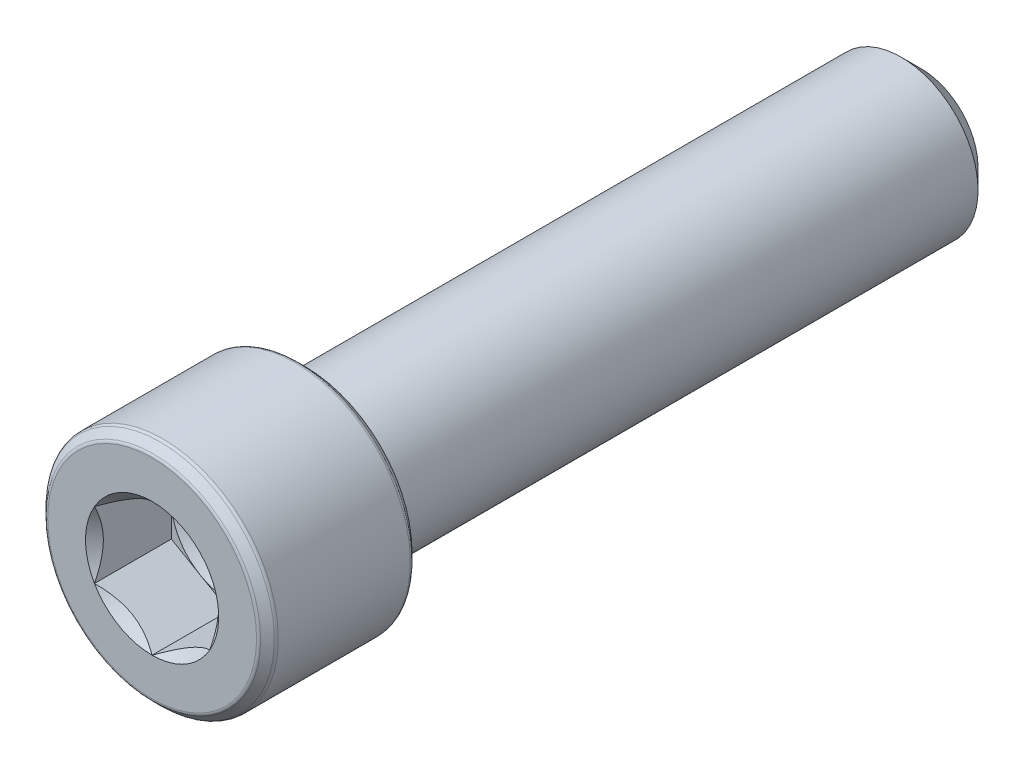
SolidWorks part; units mm, degrees
ref_plane "Front Plane" through (0, 0, 0) normal (0, 0, 1) x (1, 0, 0)
ref_plane "Top Plane" through (0, 0, 0) normal (0, 1, 0) x (1, 0, 0)
ref_plane "Right Plane" through (0, 0, 0) normal (1, 0, 0) x (0, 0, -1)
sketch "Sketch1" plane through (0, 0, 0) normal (1, 0, 0) x (0, 0, -1)
  line L0 (-15.875, 0) -> (15.875, 0) construction
  line L1 (-15.875, -4.7625) -> (-15.875, 4.7625) construction
  line L2 (-15.875, 4.7625) -> (-9.525, 4.7625) construction
  line L3 (-9.525, 4.7625) -> (-9.525, 3.175) construction
  line L4 (-9.525, 3.175) -> (15.0501, 3.175) construction
  line L5 (15.7956, 3.3125) -> (16.4306, 2.2126) construction
  line L6 (16.4306, 2.2126) -> (17.0656, 3.3125) construction
  line L7 (17.0656, 3.3125) -> (15.7956, 3.3125) construction
  line L8 (15.0501, 3.175) -> (15.875, 2.3501) construction
  line L9 (15.875, 2.3501) -> (15.875, 0) construction
  line L10 (15.875, 3.175) -> (16.9863, 3.175) construction
  line L11 (16.4306, 3.3125) -> (16.4306, 3.175) construction
  line L12 (16.4306, 3.175) -> (16.4306, 2.3501) construction
  line L13 (16.4306, 2.3501) -> (16.4306, 2.2126) construction
  line L14 (16.3513, 2.3501) -> (16.51, 2.3501) construction
  line L15 (15.8353, 3.2437) -> (17.0259, 3.2437) construction
  line L16 (16.51, 2.3501) -> (17.0259, 3.2437) construction
  line L17 (16.3513, 2.3501) -> (15.8353, 3.2437) construction
  line L18 (-15.875, 2.3812) -> (-12.7, 2.3812) construction
  line L19 (-12.7, 2.3812) -> (-12.7, 0) construction
  line L20 (12.7, 3.175) -> (12.7, -3.175) construction
  line L21 (-15.875, -2.3813) -> (-15.875, 2.3812) construction
  line L22 (15.875, -3.175) -> (15.875, 3.175) construction
  point P20 (16.4306, 3.2437)
  point P22 (12.7, -3.175)
  point P28 (12.7, 0)
  point P29 (15.0501, -3.175)
  point P30 (-11.1125, 4.7625)
  point P36 (-15.875, 0)
  point P38 (15.875, 0)
  dimension "Length" = 25.4
  dimension "Head Height" = 6.35
  dimension "D1" = 45
  dimension "Thread Pitch" = 1.27
  dimension "D3" = 0.1588
  dimension "D4" = 3.175
  dimension "D5" = 3.175
  dimension "D2" = 4.7625
  dimension "Head Diameter" = 9.525
  dimension "Drive Size" = 4.7625
  dimension "Screw Size Decimal Equivalent" = 6.35
sketch "Sketch3" plane through (0, 0, 0) normal (1, 0, 0) x (0, 0, -1)
  line L0 (-15.875, 4.3125) -> (-15.875, 2.3812)
  line L1 (-15.875, 2.3812) -> (-12.7, 2.3812)
  line L2 (-12.7, 2.3812) -> (-12.7, 0)
  line L3 (-12.7, 0) -> (15.875, 0)
  line L4 (15.875, 0) -> (15.875, 2.3501)
  line L5 (15.875, 2.3501) -> (15.0501, 3.175)
  line L6 (15.0501, 3.175) -> (-9.525, 3.175)
  line L7 (-9.525, 3.175) -> (-9.525, 4.3125)
  line L8 (-9.975, 4.7625) -> (-15.425, 4.7625)
  line L9 (-15.8262, 4.4303) -> (-15.5428, 4.7137)
  line L10 (-9.8572, 4.7137) -> (-9.5738, 4.4303)
  line L11 (-15.875, 4.7625) -> (-9.525, 4.7625) construction
  arc A0 (-15.5428, 4.7137) -> (-15.425, 4.7625) centre (-15.425, 4.5958) cw
  arc A1 (-15.8262, 4.4303) -> (-15.875, 4.3125) centre (-15.7083, 4.3125) ccw
  arc A2 (-9.5738, 4.4303) -> (-9.525, 4.3125) centre (-9.6917, 4.3125) cw
  arc A3 (-9.8572, 4.7137) -> (-9.975, 4.7625) centre (-9.975, 4.5958) ccw
  point P25 (-15.875, 4.3815)
  dimension "D1" = 45
  dimension "D3" = 0.1667
  dimension "D2" = 0.381
revolve "Revolve1" add sketch "Sketch3" angle 360 about L0
sketch "Sketch4" plane through (0, 0, 15.875) normal (0, 0, 1) x (1, 0, 0)
  line L1 (0, 2.7496) -> (-2.3812, 1.3748)
  line L2 (-2.3812, 1.3748) -> (-2.3812, -1.3748)
  line L3 (-2.3812, -1.3748) -> (0, -2.7496)
  line L4 (0, -2.7496) -> (2.3812, -1.3748)
  line L5 (2.3812, -1.3748) -> (2.3812, 1.3748)
  line L6 (2.3812, 1.3748) -> (0, 2.7496)
  circle A0 centre (0, 0) radius 2.3812 construction
extrude "Cut-Extrude1" cut sketch "Sketch4" against normal up to vertex (3.175 mm away) up to point (0, 2.3812, 12.7)
sketch "Sketch5" plane through (0, 0, 15.875) normal (0, 0, 1) x (1, 0, 0)
  circle A0 centre (0, 0) radius 2.7496
extrude "Cut-Extrude2" cut sketch "Sketch5" against normal up to next (3.175 mm away) draft 45
sketch "Sketch10" plane through (0, 0, 12.7) normal (0, 0, 1) x (1, 0, 0)
  line L0 (2.3812, 1.3748) -> (2.3812, -1.3748) construction
  circle A0 centre (0, 0) radius 2.3812
extrude "Cut-Extrude3" cut sketch "Sketch10" against normal through all draft 60
ref_plane "Plane1" [suppressed] through (0, 0, 9.3663) normal (0, 0, -1) x (-1, 0, 0)
split "Split1" [suppressed] bodies to split 112
sketch "Sketch6" [suppressed] plane through (0, 0, -15.875) normal (0, 0, -1) x (-1, 0, 0)
  circle A0 centre (0, 0) radius 3.175 construction
  circle A1 centre (0, 0) radius 3.175
curve "Helix/Spiral1" [suppressed] pitch 1.27 height 26.67 turns 21
sketch "Sketch7" [suppressed] plane through (0, 0, 0) normal (1, 0, 0) x (0, 0, -1)
  line L0 (16.3513, 2.3501) -> (16.51, 2.3501) construction
  line L1 (16.3513, 2.3501) -> (15.8353, 3.2437) construction
  line L2 (15.8353, 3.2437) -> (17.0259, 3.2437) construction
  line L3 (16.51, 2.3501) -> (17.0259, 3.2437) construction
  line L4 (16.3513, 2.3501) -> (16.51, 2.3501)
  line L5 (16.3513, 2.3501) -> (15.8353, 3.2437)
  line L6 (15.8353, 3.2437) -> (17.0259, 3.2437)
  line L7 (16.51, 2.3501) -> (17.0259, 3.2437)
sweep "Cut-Sweep1" [suppressed] cut profiles "Sketch7" path "Helix/Spiral1"
sketch "Sketch14" [suppressed] plane through (0, 0, 9.3663) normal (0, 0, -1) x (-1, 0, 0)
  circle A1 centre (0, 0) radius 3.175
  circle A2 centre (0, 0) radius 3.175
  dimension "D1" = 0
extrude "Boss-Extrude2" [suppressed] add sketch "Sketch14" along normal through all draft 60.148
sketch "Sketch12" [suppressed] plane through (0, 0, 15.875) normal (0, 0, 1) x (1, 0, 0)
  line L0 (0, 0) -> (0, 4.7625) construction
  line L1 (0, 0) -> (0.2381, 5.0858) construction
  line L2 (0.2381, 5.0858) -> (-0.2381, 5.0858)
  line L3 (-0.2381, 5.0858) -> (0, 0) construction
  line L4 (-0.2381, 5.0858) -> (-0.055, 4.6461)
  line L5 (0.055, 4.6461) -> (0.2381, 5.0858)
  line L7 (0, 4.3125) -> (0, 4.4303) construction
  circle A0 centre (0, 0) radius 4.7625 construction
  arc A2 (-0.055, 4.6461) -> (0.055, 4.6461) centre (0, 4.669) ccw
  point P11 (0, 4.5143)
  point P13 (0, 4.6095)
  point P17 (0, 4.3714)
  dimension "D3" = 0.0595
  dimension "D1" = 0.4763
  dimension "D2" = 5.361
  dimension "D5" = 0.2381
extrude "Cut-Extrude4" [suppressed] cut sketch "Sketch12" against normal blind 4.7625
sketch "Sketch13" [suppressed] plane through (0, 0, 11.1125) normal (0, 0, 1) x (1, 0, 0)
  circle A0 centre (0, 0) radius 4.7625
  circle A2 centre (0, 0) radius 3.175
  arc A3 (0.103, 4.7614) -> (-0.103, 4.7614) centre (0, 0) ccw construction
extrude "Boss-Extrude1" [suppressed] add sketch "Sketch13" along normal through all draft 45
pattern_circular "CirPattern1" [suppressed] count 72 over 360 about axis through (0, 0, 15.875) along (0, 0, -1) of bodies 116
equation "\"D3@Sketch1\" = \"Thread Pitch@Sketch1\" / 8"
equation "\"D4@Sketch1\"=\"Thread Pitch@Sketch1\" * 2.5"
equation "\"D3@Helix/Spiral1\"=\"Length@Sketch1\" + \"Thread Pitch@Sketch1\""
equation "\"D4@Helix/Spiral1\" = \"Thread Pitch@Sketch1\""
equation "\"D5@Sketch1\"=\"Head Height@Sketch1\"*0.5"
equation "\"D2@Sketch3\"=\"Head Diameter@Sketch1\" /25"
equation "\"D1@Sketch12\"=\"Head Diameter@Sketch1\"*0.05"
equation "\"D1@CirPattern1\"=int(360/\"D2@Sketch12\")+5"
equation "\"D3@Sketch12\"=\"D1@Sketch12\"*0.125"
equation "\"D3@Sketch3\"=\"D2@Sketch3\"*0.4375"
equation "\"D5@Sketch12\"=\"D2@Sketch3\"*0.625"
equation "\"D1@Cut-Extrude4\"=\"D2@Sketch1\""
equation "\"D2@Sketch1\"=\"Head Height@Sketch1\"*0.75"
equation "\"D1@Plane1\"=\"Thread Pitch@Sketch1\"*0.125"
equation "\"Pitch Natural Taper Angle\"= ATN ( \"Thread Pitch@Sketch1\" / 2 )"
equation "\"Angle Count\"= 60 / \"Pitch Natural Taper Angle\""
equation "\"Rounded Angle Count\"= ROUND ( \"Angle Count\" )"
equation "\"Taper Angle\"= \"Rounded Angle Count\" * \"Pitch Natural Taper Angle\""
equation "\"D3@Boss-Extrude2\"=\"Taper Angle\""
